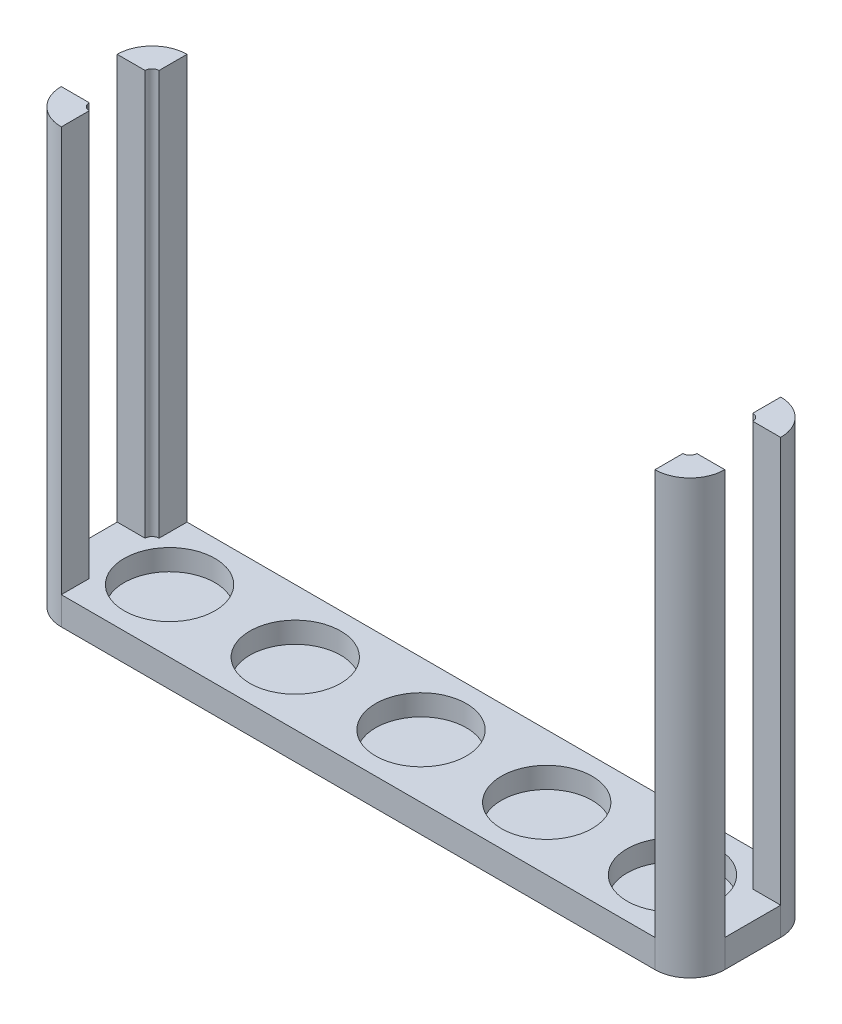
SolidWorks part; units mm, degrees
ref_plane "Front Plane" through (0, 0, 0) normal (0, 0, 1) x (1, 0, 0)
ref_plane "Top Plane" through (0, 0, 0) normal (0, 1, 0) x (1, 0, 0)
ref_plane "Right Plane" through (0, 0, 0) normal (1, 0, 0) x (0, 0, -1)
sketch "Sketch5" plane through (0, 0, 0) normal (0, 1, 0) x (1, 0, 0)
  line L1 (0, 0) -> (190, 0)
  line L2 (0, 0) -> (0, 36)
  line L3 (0, 36) -> (190, 36)
  line L4 (190, 0) -> (190, 36)
  dimension "D1" = 36
  dimension "D2" = 190
extrude "Boss-Extrude1" add sketch "Sketch5" along normal blind 8
sketch "Sketch6" plane through (0, 8, 0) normal (0, 1, 0) x (1, 0, 0)
  circle A0 centre (23, 18) radius 13
  circle A1 centre (59, 18) radius 13
  circle A2 centre (95.0046, 18) radius 13
  circle A3 centre (131.0046, 18) radius 13
  circle A4 centre (167.0023, 18) radius 12.9977
  point P6 (10, 18)
  point P7 (180, 18)
extrude "Cut-Extrude1" cut sketch "Sketch6" against normal blind 6
sketch "Sketch7" plane through (0, 8, 0) normal (0, 1, 0) x (1, 0, 0)
  line L1 (0, 0) -> (10, 0)
  line L2 (0, 0) -> (0, 10)
  line L3 (0, 10) -> (8, 10)
  line L4 (10, 0) -> (10, 8)
  line L5 (0, 36) -> (10, 36)
  line L6 (0, 36) -> (0, 26)
  line L7 (0, 26) -> (8, 26)
  line L8 (10, 36) -> (10, 28)
  line L9 (190, 36) -> (180, 36)
  line L10 (190, 36) -> (190, 26)
  line L11 (190, 26) -> (182, 26)
  line L12 (180, 36) -> (180, 28)
  line L13 (190, 0) -> (180, 0)
  line L14 (190, 0) -> (190, 10)
  line L15 (190, 10) -> (182, 10)
  line L16 (180, 0) -> (180, 8)
  arc A1 (180, 28) -> (182, 26) centre (180, 26) cw
  arc A2 (180, 8) -> (182, 10) centre (180, 10) ccw
  arc A3 (8, 10) -> (10, 8) centre (10, 10) ccw
  arc A4 (8, 26) -> (10, 28) centre (10, 26) cw
  point P36 (0, 0)
  dimension "D10" = 4
  dimension "D11" = 2
  dimension "D2" = 2
  dimension "D1" = 10
  dimension "D3" = 10
  dimension "D4" = 10
  dimension "D6" = 10
  dimension "D7" = 10
  dimension "D8" = 10
  dimension "D9" = 10
extrude "Boss-Extrude2" add sketch "Sketch7" along normal blind 116
fillet "Fillet1" radius 10 4 edges at (190, 62, 0) (190, 62, -36) (0, 62, -36) (0, 62, 0)
